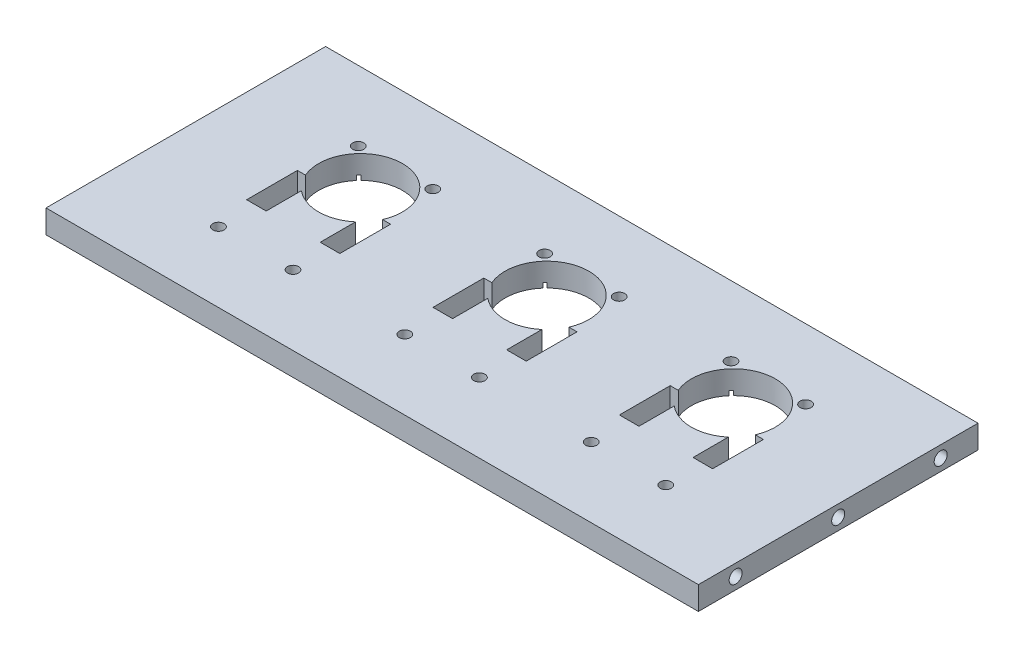
SolidWorks part; units mm, degrees
material "PET"
ref_plane "前视基准面" through (0, 0, 0) normal (0, 0, 1) x (1, 0, 0)
ref_plane "上视基准面" through (0, 0, 0) normal (0, 1, 0) x (1, 0, 0)
ref_plane "右视基准面" through (0, 0, 0) normal (1, 0, 0) x (0, 0, -1)
sketch "草图1" plane through (0, 0, 0) normal (0, 1, 0) x (1, 0, 0)
  line L0 (0, 0) -> (140, 0)
  line L1 (140, 0) -> (140, -60)
  line L2 (140, -60) -> (0, -60)
  line L3 (0, -60) -> (0, 0)
  dimension "D1" = 140
  dimension "D2" = 60
extrude "凸台-拉伸1" add sketch "草图1" along normal blind 5
ref_plane "基准面1" through (0, 0, 30) normal (0, 0, 1) x (1, 0, 0)
sketch "草图2" plane through (0, 5, 0) normal (0, 1, 0) x (1, 0, 0)
  line L0 (140, -30) -> (140, -13) construction
  line L1 (140, -60) -> (140, 0) construction
  line L2 (140, -30) -> (140, -47) construction
  line L3 (0, -13) -> (30, -13) construction
  line L4 (0, 0) -> (0, -60) construction
  line L5 (0, -13) -> (0, -47) construction
  line L6 (0, -47) -> (140, -47) construction
  line L7 (100, -13) -> (120, -13) construction
  line L8 (100, -13) -> (100, -47) construction
  line L9 (120, -13) -> (120, -47) construction
  line L10 (110, -13) -> (110, -15) construction
  line L11 (102, -15) -> (118, -15) construction
  line L12 (-2.75, -30) -> (2.75, -30) construction
  line L13 (100, -13) -> (140, -13) construction
  line L14 (100, -26.05) -> (100, -36.95)
  line L15 (100, -26.05) -> (101.7297, -26.05)
  line L16 (104.2, -29.3819) -> (104.2, -36.95)
  line L17 (104.2, -36.95) -> (100, -36.95)
  line L18 (120, -26.05) -> (118.2703, -26.05)
  line L19 (115.8, -29.3819) -> (115.8, -36.95)
  line L20 (115.8, -36.95) -> (120, -36.95)
  line L21 (120, -36.95) -> (120, -26.05)
  line L22 (110, -31.5) -> (110, -47) construction
  circle A0 centre (102, -15) radius 1.2
  circle A1 centre (118, -15) radius 1.2
  circle A2 centre (102, -45) radius 1.2
  circle A3 centre (118, -45) radius 1.2
  arc A4 (104.2, -29.3819) -> (115.8, -29.3819) centre (110, -22.5) ccw
  arc A5 (118.2703, -26.05) -> (101.7297, -26.05) centre (110, -22.5) ccw
  point P22 (110, -15)
  point P28 (110, -22.5)
  dimension "D12" = 2.4
  dimension "D13" = 2.4
  dimension "D15" = 13.05
  dimension "D1" = 17
  dimension "D2" = 17
  dimension "D3" = 140
  dimension "D4" = 13.05
  dimension "D5" = 10.9
  dimension "D6" = 20
  dimension "D7" = 20
  dimension "D10" = 16
  dimension "D11" = 15
  dimension "D14" = 9.5
  dimension "D16" = 23.95
  dimension "D17" = 10.9
extrude "电机孔位" cut sketch "草图2" against normal through all
ref_plane "基准面2" through (0, 2.5, 0) normal (0, 1, 0) x (1, 0, 0)
ref_axis "基准轴1" through (140, 5, 60) along (0, 0, -1)
ref_axis "基准轴2" through (140, 5, 60) along (0, -1, 0)
ref_point "点1"
sketch "草图4" plane through (0, 0, 0) normal (-1, 0, 0) x (0, 0, 1)
  line L0 (0, 5) -> (0, 0) construction
  line L1 (0, 2.5) -> (60, 2.5) construction
  line L2 (60, 5) -> (60, 0) construction
  line L3 (33, 2.5) -> (-33, 2.5) construction
  line L4 (60, 5) -> (60, 0) construction
  circle A0 centre (30, 2.5) radius 1.4
  circle A1 centre (8, 2.5) radius 1.4
  circle A2 centre (52, 2.5) radius 1.4
  dimension "D1" = 8
  dimension "D2" = 2.8
  dimension "D3" = 2.8
  dimension "D4" = 2.8
  dimension "D5" = 8
extrude "切除-拉伸3" cut sketch "草图4" against normal blind 5
ref_plane "基准面3" through (70, 0, 0) normal (1, 0, 0) x (0, 0, -1)
mirror "镜向1" about plane through (70, 0, 0) normal (1, 0, 0) of "切除-拉伸3"
pattern_linear "阵列(线性)1" count 3 spacing 40 along (-1, 0, 0) of "电机孔位"
sketch "草图6" plane through (0, 0, 0) normal (0, -1, 0) x (1, 0, 0)
  circle A0 centre (22, 45) radius 2
  circle A1 centre (38, 45) radius 2
  circle A2 centre (62, 45) radius 2
  circle A3 centre (78, 45) radius 2
  circle A4 centre (102, 45) radius 2
  circle A5 centre (118, 45) radius 2
  circle A6 centre (22, 15) radius 2
  circle A7 centre (38, 15) radius 2
  circle A8 centre (62, 15) radius 2
  circle A9 centre (78, 15) radius 2
  circle A10 centre (102, 15) radius 2
  circle A11 centre (118, 15) radius 2
  dimension "D1" = 4
extrude "切除-拉伸4" cut sketch "草图6" against normal blind 1
